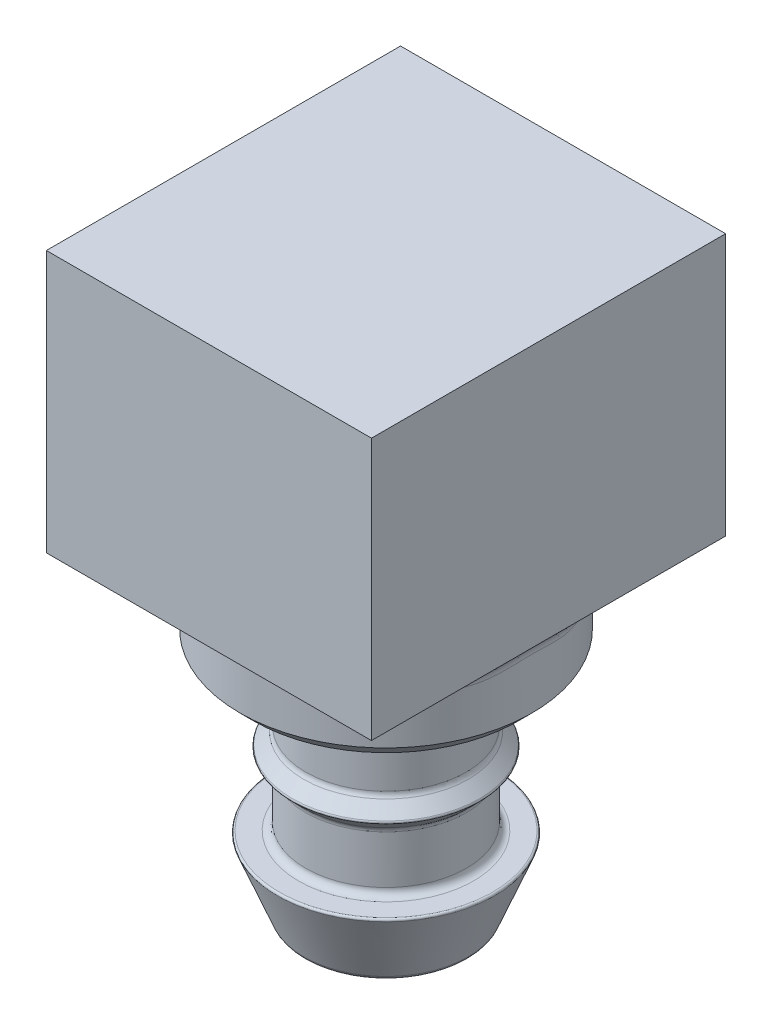
SolidWorks part; units mm, degrees
ref_plane "Front Plane" through (0, 0, 0) normal (0, 0, 1) x (1, 0, 0)
ref_plane "Top Plane" through (0, 0, 0) normal (0, 1, 0) x (1, 0, 0)
ref_plane "Right Plane" through (0, 0, 0) normal (1, 0, 0) x (0, 0, -1)
sketch "Sketch1" plane through (0, 0, 0) normal (0, 0, 1) x (1, 0, 0)
  line L0 (0, 1017.6623) -> (0, 12.7) construction
  line L1 (0, -12.7) -> (4.3656, -12.7)
  line L3 (4.3656, 0) -> (7.9375, 0)
  line L4 (7.9375, 0) -> (7.9375, 3.9688)
  line L8 (0, 3.9688) -> (0, -12.7)
  line L9 (4.3656, -12.7) -> (5.9531, -8.7312)
  line L22 (7.9375, 0) -> (7.9375, 3.9688) construction
  line L25 (7.9375, 6.35) -> (0, 6.35) construction
  line L27 (6.35, 3.9688) -> (7.9375, 3.9688)
  line L32 (5.9531, -8.7312) -> (4.3656, -8.7312)
  line L33 (4.3656, -8.7312) -> (4.3656, -5.5563)
  line L34 (4.3656, -3.9687) -> (5.1594, -4.7625)
  line L35 (5.1594, -4.7625) -> (4.3656, -5.5563)
  line L36 (5.1594, -4.7625) -> (4.3656, -4.7625) construction
  line L37 (4.3656, -3.9687) -> (4.3656, 0)
  line L38 (6.35, 3.9688) -> (0, 3.9688)
  line L40 (0, 3.9688) -> (0, -7.7377) construction
  dimension "D7" = 1.5875
  dimension "D1" = 12.7
  dimension "D2" = 3.9688
  dimension "D6" = 15.875
  dimension "D8" = 8.7312
  dimension "D10" = 7.9375
  dimension "D11" = 45
  dimension "D9" = 0.7937
revolve "Revolve1" add sketch "Sketch1" angle 360 about L0
fillet "Fillet3" radius 0.3969 5 edges at (0, -12.7, 4.3656) (0, -8.7313, 4.3656) (0, 0, 4.3656) (0, -3.9688, 4.3656) (0, -5.5562, 4.3656)
fillet "Fillet4" radius 0.0992 2 edges at (0, -8.7313, 5.9531) (0, -4.7625, 5.1594)
ref_plane "Plane1" through (0, 3.9688, 0) normal (0, 1, 0) x (1, 0, 0)
sketch "Sketch2" plane through (0, 3.9688, 0) normal (0, 1, 0) x (1, 0, 0)
  line L0 (0, 9.6273) -> (0, -9.6273) construction
  line L9 (9.0227, 0) -> (-9.0227, 0) construction
  line L11 (8.8366, 9.6273) -> (-8.8366, 9.6273)
  line L12 (8.8366, 9.6273) -> (8.8366, -9.6273)
  line L13 (8.8366, -9.6273) -> (-8.8366, -9.6273)
  line L14 (-8.8366, 9.6273) -> (-8.8366, -9.6273)
  line L15 (8.8366, 9.6273) -> (-8.8366, -9.6273) construction
  line L16 (8.8366, -9.6273) -> (-8.8366, 9.6273) construction
  point P0 (0, 0)
  point P1 (0, 0)
  point P2 (0, 0)
  point P6 (0, 0)
  point P11 (0, 0)
extrude "Boss-Extrude1" add sketch "Sketch2" along normal blind 15
sketch "Sketch3" plane through (0, -12.7, 0) normal (0, -1, 0) x (1, 0, 0)
  circle A0 centre (0, 0) radius 2.413
extrude "Cut-Extrude1" cut sketch "Sketch3" against normal blind 27
sketch "Sketch5" plane through (0, 0, 0) normal (1, 0, 0) x (0, 0, -1)
  line L0 (0, 18.9688) -> (0, 3.9688) construction
  line L1 (9.6273, 18.9688) -> (-9.6273, 18.9688) construction
  line L2 (55, 3.9688) -> (-55, 3.9688) construction
  circle A0 centre (0, 11.4688) radius 2.25
  dimension "D1" = 4.5
extrude "Cut-Extrude3" cut sketch "Sketch5" against normal blind 22.86
chamfer "Chamfer2" distance 0.762 angle 45 5 edges at (8.8366, 3.9688, 0) (0, 3.9688, -9.6273) (-8.8366, 3.9688, 0) (0, 3.9688, 9.6273) (0, 0, 7.9375)
fillet "Fillet6" radius 0.762 1 edges at (0, 3.9688, 7.9375)
